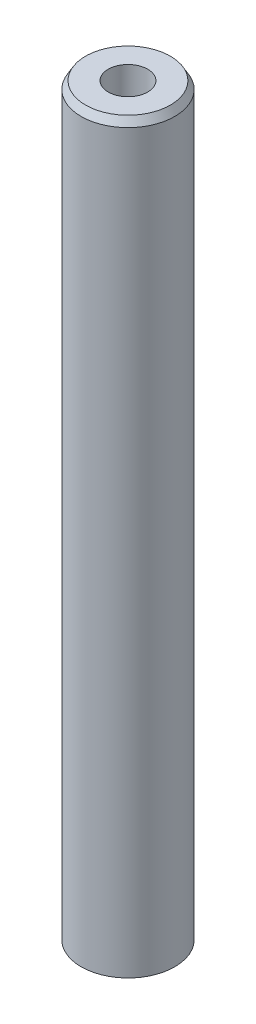
SolidWorks part; units mm, degrees
ref_plane "Front Plane" through (0, 0, 0) normal (0, 0, 1) x (1, 0, 0)
ref_plane "Top Plane" through (0, 0, 0) normal (0, 1, 0) x (1, 0, 0)
ref_plane "Right Plane" through (0, 0, 0) normal (1, 0, 0) x (0, 0, -1)
sketch "Sketch1" plane through (0, 0, 0) normal (0, 1, 0) x (1, 0, 0)
  circle A0 centre (0, 0) radius 20
  dimension "SHAFT_OD" = 40
extrude "Boss-Extrude1" add sketch "Sketch1" along normal blind 319.7614
sketch "Sketch2" plane through (0, 0, 0) normal (0, 1, 0) x (1, 0, 0)
  circle A0 centre (0, 0) radius 8.4505
  dimension "BORE_D" = 16.9011
extrude "Cut-Extrude1" cut sketch "Sketch2" along normal through all
chamfer "Chamfer1" distance 3.2685 angle 30 2 edges at (0, 319.7614, 20) (0, 0, 20) first distance on face at (0, 319.7614, 20) first distance on face at (0, 0, 8.4505)
